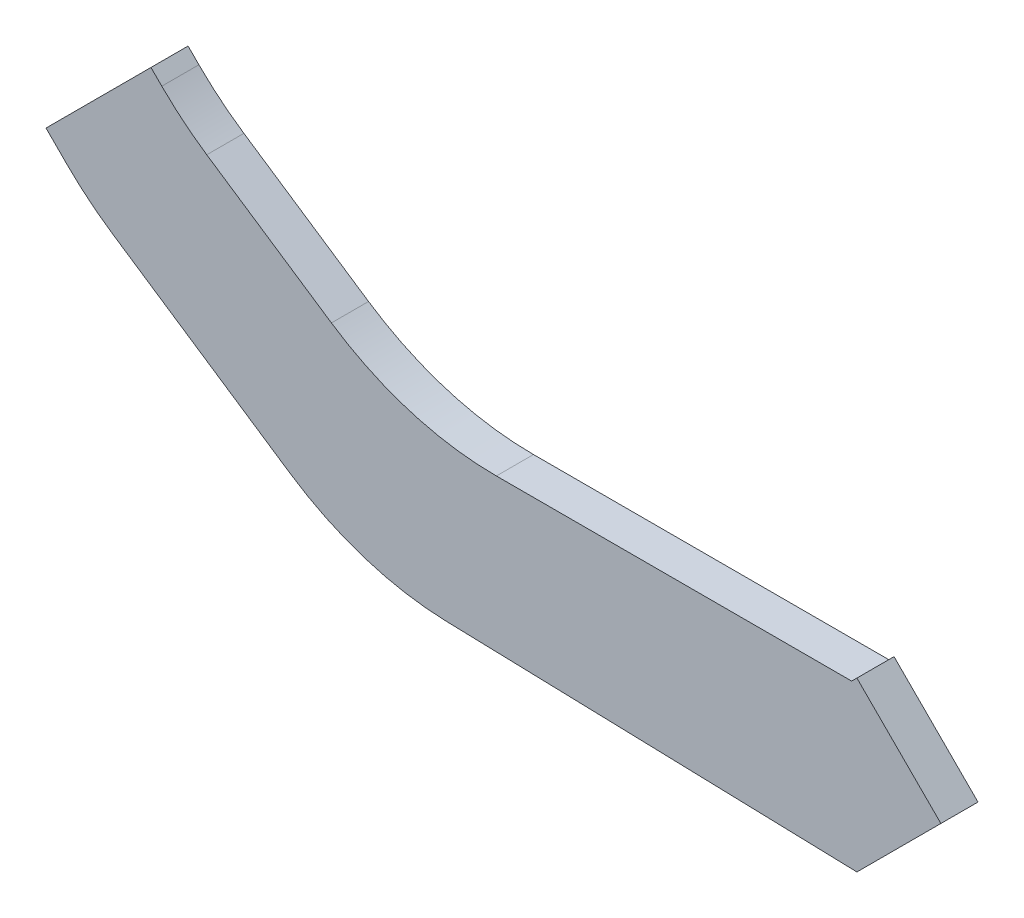
SolidWorks part; units mm, degrees
material "PBT General Purpose"
ref_plane "Front Plane" through (0, 0, 0) normal (0, 0, 1) x (1, 0, 0)
ref_plane "Top Plane" through (0, 0, 0) normal (0, 1, 0) x (1, 0, 0)
ref_plane "Right Plane" through (0, 0, 0) normal (1, 0, 0) x (0, 0, -1)
sketch "frame_outline" plane through (0, 0, 0) normal (0, 0, 1) x (1, 0, 0)
  line L0 (-1.8031, -1.8738) -> (-1.591, -2.086)
  line L1 (0, 0) -> (0.3, 0) construction
  line L2 (-2.5102, -2.5809) -> (-2.2285, -2.8627)
  line L3 (0, 0) -> (4.9667, -4.9667) construction
  line L84 (-1.591, -2.086) -> (-0.0832, -3.0936)
  line L85 (-2.2285, -2.8627) -> (-0.3866, -4.0936)
  line L87 (0, 0) -> (-3.6266, -3.6266) construction
  line L88 (2.9522, -3.0582) -> (3.5179, -3.6239)
  line L89 (2.9522, -3.0582) -> (2.9168, -3.0936)
  line L90 (2.9168, -3.0936) -> (-0.0832, -3.0936)
  line L91 (3.5179, -3.6239) -> (2.9522, -4.1896)
  line L92 (-1.8031, -1.8738) -> (-2.5102, -2.5809)
  line L93 (-0.3866, -4.0936) -> (2.9522, -4.1896)
  dimension "D2" = 0.3
  dimension "D4" = 45
  dimension "D18" = 45
  dimension "D19" = 0.075
  dimension "D20" = 0.05
  dimension "D17" = 4.25
  dimension "D21" = 0.8
  dimension "D22" = 0.8
  dimension "D23" = 1
  dimension "D24" = 0.05
  dimension "D3" = 2.6
  dimension "D5" = 3
  dimension "D6" = 0.3
  dimension "D7" = 1
  dimension "D8" = 1
extrude "Boss-Extrude1" add sketch "frame_outline" along normal mid plane 0.25
fillet "Fillet1" radius 2 4 edges at (-2.2285, -2.8627, 0) (-0.3866, -4.0936, 0) (-1.591, -2.086, 0) (-0.0832, -3.0936, 0)
equation "\"t\"= 0.25'thickness of the sheets"
equation "\"t_cf\" = 0.115'thickness of single carbon fiber layer"
equation "\"t_kapton\" = 0.025'thickness of single Kapton flex layer"
equation "\"t_fr4\" = 0.1'thickness of FR4 with copper layer"
equation "\"joint_flex\"= 0.1'Width of flextures gap"
equation "\"joint_flex_eff\"= 0.02'Width of flecture after castelation"
equation "\"joint_fold\"= 0.2'Width of folding joints for 90deg fold"
equation "\"gap_tolerance\"= 0.002'Width to have interfecence fit between carbon fiber inserts"
equation "\"assemble_angle\"= 90'Angle of assembly parts"
equation "\"D1@Boss-Extrude1\"=\"t\""
equation "\"link_lift\"= 0.5'Actuation linkage amplification for the lift motion"
equation "\"link_swing\"= 0.45'Actuation linkage amplification for the swing motion"
equation "\"D19@frame_outline\"=\"joint_fold\"-\"t\"/2"
equation "\"D17@frame_outline\"=4.2+0.05"
equation "\"D24@frame_outline\"=\"joint_flex\"/2"
